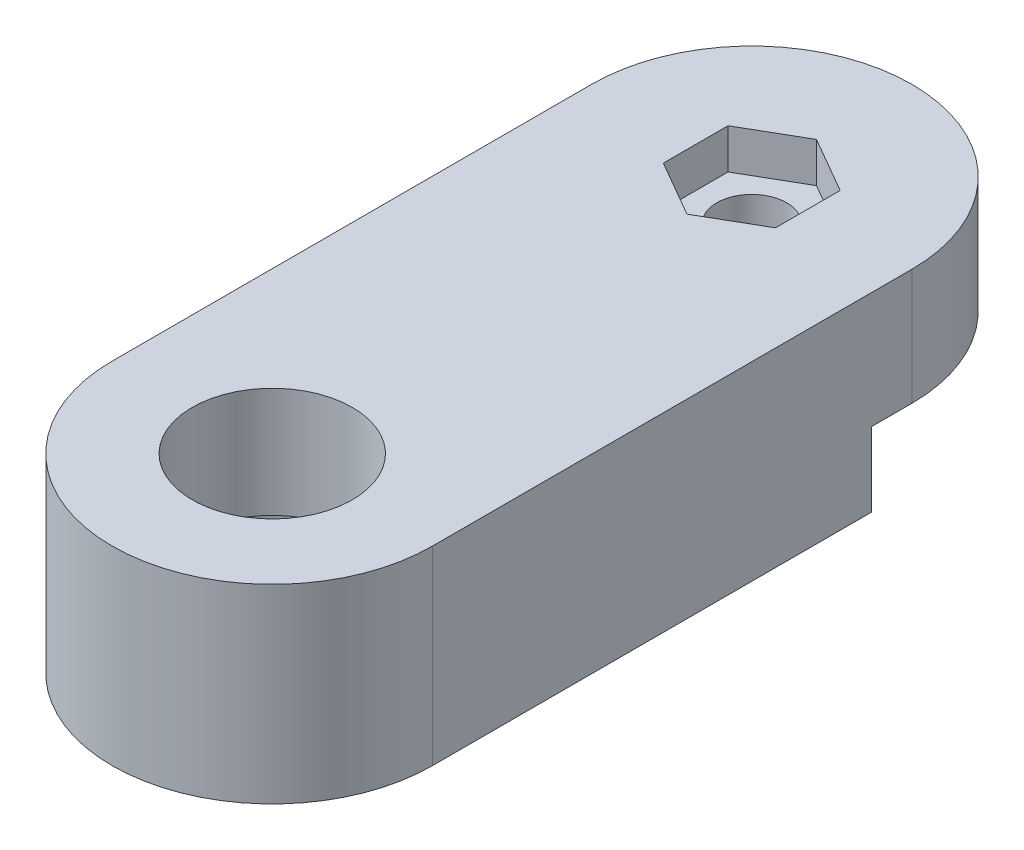
SolidWorks part; units mm, degrees
ref_plane "Front Plane" through (0, 0, 0) normal (0, 0, 1) x (1, 0, 0)
ref_plane "Top Plane" through (0, 0, 0) normal (0, 1, 0) x (1, 0, 0)
ref_plane "Right Plane" through (0, 0, 0) normal (1, 0, 0) x (0, 0, -1)
sketch "Sketch1" plane through (0, 0, 0) normal (0, 1, 0) x (1, 0, 0)
  line L0 (0, 27.4685) -> (0, -33.8565) construction
  line L1 (-8, 0) -> (-8, 23.95)
  line L2 (8, 0) -> (8, 23.95)
  circle A0 centre (0, 0) radius 8
  circle A1 centre (0, 23.95) radius 8
  circle A2 centre (0, 0) radius 5.15
  dimension "D1" = 16
  dimension "D4" = 10.3
  dimension "D2" = 23.95
extrude "Boss-Extrude1" add sketch "Sketch1" along normal blind 4 contours A1 L0 A0 L2 | L0 A1 L1 A0 | A1 L0 | L0 A1 | L0 A0 A2 | A0 L0 A2 region at (4.6675, 0, -11.975) region at (-4.6675, 0, -11.975) region at (-5.4969, 0, -18.4531) region at (5.5304, 0, -5.5304) region at (-0.1789, 0, -6.575)
sketch "Sketch2" plane through (0, 4, 0) normal (0, 1, 0) x (1, 0, 0)
  line L2 (-8, 23.95) -> (-8, 0)
  line L3 (8, 0) -> (8, 23.95)
  line L4 (-8, 23.95) -> (-8, 0)
  line L5 (8, 0) -> (8, 23.95)
  circle A0 centre (0, 0) radius 4
  arc A3 (-8, 0) -> (8, 0) centre (0, 0) ccw
  arc A4 (8, 23.95) -> (-8, 23.95) centre (0, 23.95) ccw
  arc A5 (-8, 0) -> (8, 0) centre (0, 0) ccw
  arc A6 (8, 23.95) -> (-8, 23.95) centre (0, 23.95) ccw
  dimension "D1" = 8
  dimension "D2" = 0
extrude "Boss-Extrude2" add sketch "Sketch2" along normal offset from surface (5.5 mm away) 9.5 up to face at (0, 0, -11.975)
sketch "Sketch3" plane through (0, 0, 0) normal (0, 1, 0) x (1, 0, 0)
  circle A0 centre (0, 23.95) radius 8.25
  arc A2 (8, 23.95) -> (-8, 23.95) centre (0, 23.95) ccw construction
  dimension "D1" = 16.5
extrude "Cut-Extrude1" cut sketch "Sketch3" along normal offset from surface (3.7 mm away) 5.8 up to face at (0, 9.5, 4)
sketch "Sketch4" plane through (0, 3.7, 0) normal (0, -1, 0) x (1, 0, 0)
  circle A0 centre (0, -23.95) radius 1.75
  dimension "D1" = 3.5
extrude "Cut-Extrude2" cut sketch "Sketch4" against normal up to next
sketch "Sketch5" plane through (0, 3.7, 0) normal (0, -1, 0) x (1, 0, 0)
  circle A0 centre (0, -23.95) radius 4.1
  circle A1 centre (0, -23.95) radius 1.75 construction
  circle A2 centre (0, -23.95) radius 1.75
  dimension "D1" = 8.2
extrude "Boss-Extrude3" add sketch "Sketch5" along normal blind 0.2
sketch "Sketch6" plane through (0, 9.5, 0) normal (0, 1, 0) x (1, 0, 0)
  line L0 (-8, 23.95) -> (-8, 0) construction
  line L1 (0, 20.7168) -> (2.8, 22.3334)
  line L2 (2.8, 22.3334) -> (2.8, 25.5666)
  line L3 (2.8, 25.5666) -> (0, 27.1832)
  line L4 (0, 27.1832) -> (-2.8, 25.5666)
  line L5 (-2.8, 25.5666) -> (-2.8, 22.3334)
  line L6 (-2.8, 22.3334) -> (0, 20.7168)
  circle A0 centre (0, 23.95) radius 2.8 construction
  dimension "D1" = 5.6
extrude "Cut-Extrude3" cut sketch "Sketch6" against normal blind 2
